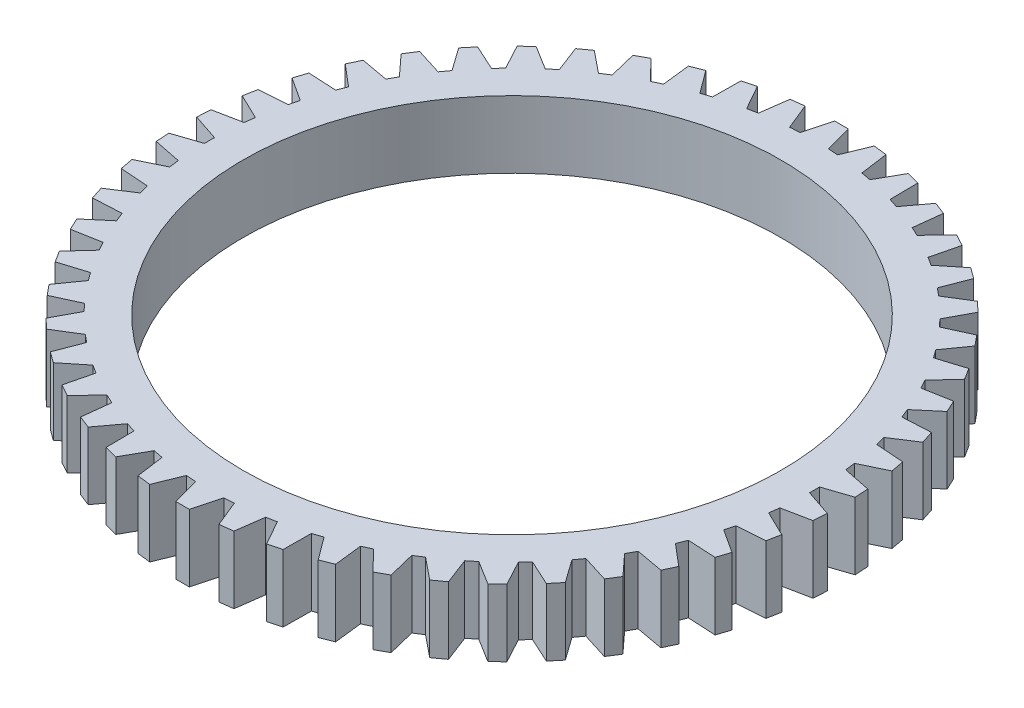
SolidWorks part; units mm, degrees
ref_plane "Front Plane" through (0, 0, 0) normal (0, 0, 1) x (1, 0, 0)
ref_plane "Top Plane" through (0, 0, 0) normal (0, 1, 0) x (1, 0, 0)
ref_plane "Right Plane" through (0, 0, 0) normal (1, 0, 0) x (0, 0, -1)
sketch "Sketch1" plane through (0, 0, 0) normal (0, 1, 0) x (1, 0, 0)
  circle A0 centre (0, 0) radius 45
  circle A1 centre (0, 0) radius 40
  dimension "D1" = 90
  dimension "D2" = 5
extrude "Boss-Extrude1" add sketch "Sketch1" along normal blind 10 contours A0 A1 region at (-43.7272, 0, 0)
sketch "Sketch2" plane through (0, 0, 0) normal (0, 1, 0) x (1, 0, 0)
  line L0 (0, 0) -> (0, 54.4054) construction
  line L1 (1, 49) -> (-1, 49)
  line L2 (-1, 49) -> (-3.4115, 40)
  line L3 (-3.4115, 40) -> (3.4115, 40)
  line L4 (1, 49) -> (3.4115, 40)
  point P8 (0, 40)
  point P9 (0, 49)
  dimension "D1" = 105
  dimension "D2" = 1
  dimension "D3" = 9
  dimension "D4" = 49
extrude "Boss-Extrude2" add sketch "Sketch2" along normal up to surface (10 mm away) up to face at (0, 10, 40)
ref_axis "Axis1" through (0, 10, 0) along (0, -1, 0)
pattern_circular "CirPattern1" count 50 over 360 about axis through (0, 10, 0) along (0, -1, 0) of "Boss-Extrude2"
